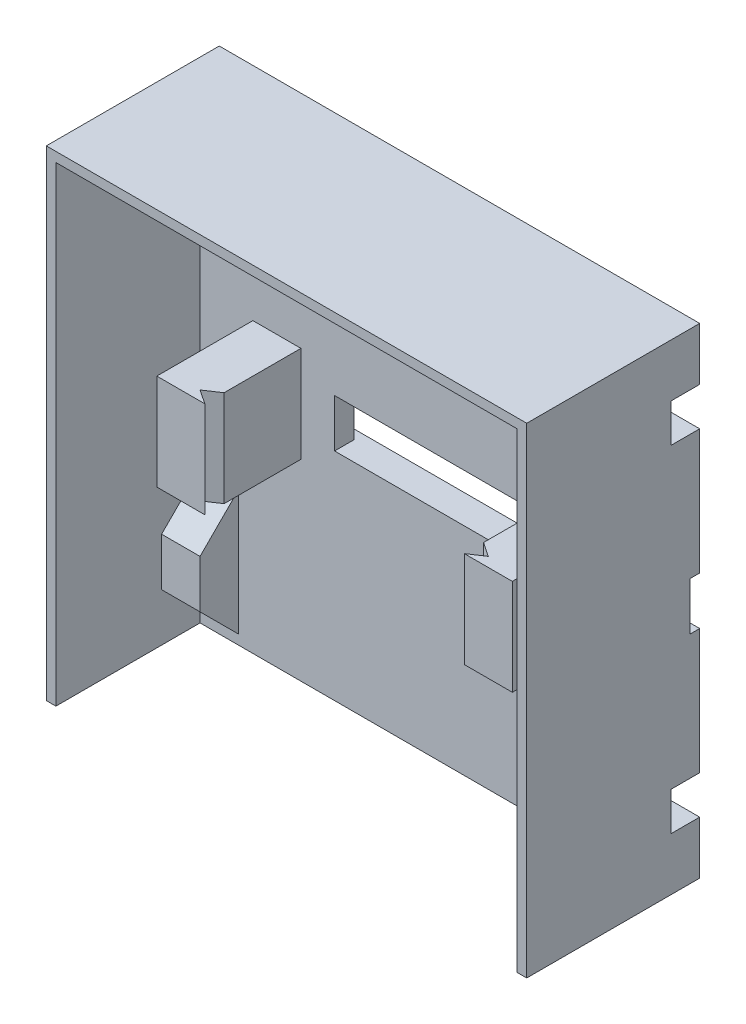
SolidWorks part; units mm, degrees
ref_plane "Přední rovina" through (0, 0, 0) normal (0, 0, 1) x (1, 0, 0)
ref_plane "Horní rovina" through (0, 0, 0) normal (0, 1, 0) x (1, 0, 0)
ref_plane "Pravá rovina" through (0, 0, 0) normal (1, 0, 0) x (0, 0, -1)
sketch "Skica1" plane through (0, 0, 0) normal (0, 0, 1) x (1, 0, 0)
  line L1 (25, 25) -> (-25, 25)
  line L2 (25, 25) -> (25, -25)
  line L3 (25, -25) -> (-25, -25)
  line L4 (-25, 25) -> (-25, -25)
  line L5 (25, 25) -> (-25, -25) construction
  line L6 (25, -25) -> (-25, 25) construction
  point P0 (0, 0)
  point P5 (-27.5, 0)
  point P11 (4.5, 0)
  dimension "D1" = 50
  dimension "D2" = 50
extrude "Přidat vysunutím2" add sketch "Skica1" along normal blind 3 contours L2 L1 L4 L3
sketch "Skica4" plane through (0, 0, 3) normal (0, 0, 1) x (1, 0, 0)
  line L1 (-10, 2.5) -> (10, 2.5)
  line L2 (-10, 2.5) -> (-10, -2.5)
  line L3 (-10, -2.5) -> (10, -2.5)
  line L4 (10, 2.5) -> (10, -2.5)
  line L5 (-10, 2.5) -> (10, -2.5) construction
  line L6 (-10, -2.5) -> (10, 2.5) construction
  line L8 (-25, 25) -> (-25, -25) construction
  point P0 (0, 0)
  dimension "D1" = 5
  dimension "D2" = 20
  dimension "D3" = 15
extrude "Odebrat vysunutím1" cut sketch "Skica4" against normal blind 2
sketch "Skica5" plane through (0, 0, 0) normal (0, 0, -1) x (-1, 0, 0)
  line L10 (25, 25) -> (25, -25) construction
  line L11 (-25, 2.5) -> (25, 2.5)
  line L12 (-25, 2.5) -> (-25, -2.5)
  line L13 (-25, -2.5) -> (25, -2.5)
  line L14 (25, 2.5) -> (25, -2.5)
  line L15 (-25, 2.5) -> (25, -2.5) construction
  line L16 (-25, -2.5) -> (25, 2.5) construction
  point P0 (0, 0)
  dimension "D1" = 5
extrude "Odebrat vysunutím3" cut sketch "Skica5" against normal blind 1 contours L11 L14 L13 L12
sketch "Skica10" plane through (0, 0, 3) normal (0, 0, 1) x (1, 0, 0)
  line L5 (-10, 2.5) -> (-10, -2.5) construction
  line L6 (-13.5, 5) -> (-18.5, 5)
  line L7 (13.5, 5) -> (18.5, 5)
  line L8 (13.5, 5) -> (13.5, -5)
  line L9 (13.5, -5) -> (18.5, -5)
  line L10 (18.5, 5) -> (18.5, -5)
  line L11 (13.5, 5) -> (18.5, -5) construction
  line L12 (13.5, -5) -> (18.5, 5) construction
  line L14 (-13.5, 5) -> (-13.5, -5)
  line L15 (-13.5, -5) -> (-18.5, -5)
  line L16 (-18.5, 5) -> (-18.5, -5)
  line L17 (-13.5, 5) -> (-18.5, -5) construction
  line L18 (-13.5, -5) -> (-18.5, 5) construction
  line L19 (10, -2.5) -> (10, 2.5) construction
  point P0 (-16, 0)
  point P5 (16, 0)
  point P10 (-13.5, 0)
  dimension "D1" = 10
  dimension "D2" = 5
  dimension "D3" = 5
  dimension "D4" = 27
  dimension "D5" = 10
  dimension "D6" = 3.5
  dimension "D7" = 3.5
  dimension "D8" = 0
extrude "Přidat vysunutím6" add sketch "Skica10" along normal blind 10
sketch "Skica12" plane through (0, 5, 0) normal (0, 1, 0) x (1, 0, 0)
  line L0 (-13.5, -13) -> (-13.5, -11)
  line L1 (-13.5, -13) -> (-13.5, -3) construction
  line L2 (-13.5, -11) -> (-15, -12)
  line L3 (-15, -12) -> (-13.5, -13)
  line L4 (13.5, -13) -> (13.5, -11)
  line L5 (13.5, -13) -> (13.5, -3) construction
  line L6 (13.5, -11) -> (15, -12)
  line L7 (15, -12) -> (13.5, -13)
  dimension "D2" = 1.5
  dimension "D1" = 2
  dimension "D3" = 1.5
extrude "Odebrat vysunutím6" cut sketch "Skica12" against normal blind 10
sketch "Skica14" plane through (0, 0, 3) normal (0, 0, 1) x (1, 0, 0)
  line L1 (-25, 25) -> (25, 25)
  line L2 (-25, 25) -> (-25, -25)
  line L3 (-25, -25) -> (25, -25)
  line L4 (25, 25) -> (25, -25)
  line L5 (-24, 24) -> (24, 24)
  line L6 (-24, 24) -> (-24, -25)
  line L7 (-24, -25) -> (24, -25)
  line L8 (24, 24) -> (24, -25)
  line M13 (-25, -25) -> (25, -25)
  line M14 (25, -25) -> (25, 25)
  line M15 (25, 25) -> (-25, 25)
  line M16 (-25, 25) -> (-25, -25)
  dimension "D1" = 1
  dimension "D2" = 1
  dimension "D3" = 1
  dimension "D4" = 0
extrude "Přidat vysunutím9" add sketch "Skica14" along normal blind 15 contours L5 L8 L6 M13 M14 M15 M16 region at (0, 24.2929, 3)
sketch "Skica17" plane through (0, 0, 1) normal (0, 0, -1) x (-1, 0, 0)
  line L0 (-25, 2.5) -> (-25, -2.5) construction
  line L1 (-10, -2.5) -> (-10, 2.5) construction
  line L2 (25, 2.5) -> (25, -2.5) construction
  circle A0 centre (-16, 0) radius 2
  circle A1 centre (16, 0) radius 2
  dimension "D1" = 4
  dimension "D2" = 4
  dimension "D3" = 9
  dimension "D4" = 6
  dimension "D5" = 9
extrude "Odebrat vysunutím8" cut sketch "Skica17" against normal blind 4
sketch "Skica18" plane through (0, 0, 0) normal (0, 0, -1) x (-1, 0, 0)
  line L0 (-25, 25) -> (-25, 2.5) construction
  line L1 (-25, 15) -> (-20, 15)
  line L2 (-25, 15) -> (-25, 20)
  line L3 (-25, 20) -> (-20, 20)
  line L4 (-20, 15) -> (-20, 20)
  line L5 (-25, 25) -> (25, 25) construction
  line L6 (-25, -2.5) -> (-25, -25) construction
  line L7 (-25, -20) -> (-20, -20)
  line L8 (-25, -20) -> (-25, -15)
  line L9 (-25, -15) -> (-20, -15)
  line L10 (-20, -20) -> (-20, -15)
  line L11 (-25, -25) -> (25, -25) construction
  line L12 (0, 25) -> (0, -25)
  line L13 (0, -25) -> (0, 25) construction
  line L14 (25, -15) -> (20, -15)
  line L15 (20, -20) -> (20, -15)
  line L16 (25, -20) -> (20, -20)
  line L17 (25, -20) -> (25, -15)
  line L18 (25, 20) -> (20, 20)
  line L19 (20, 15) -> (20, 20)
  line L20 (25, 15) -> (20, 15)
  line L21 (25, 15) -> (25, 20)
  line M11 (25, 2.5) -> (25, 25)
  line M13 (-25, 25) -> (-25, 2.5)
  dimension "D1" = 10
  dimension "D2" = 5
  dimension "D3" = 5
  dimension "D4" = 10
extrude "Přidat vysunutím10" add sketch "Skica18" against normal blind 7 contours L1 L4 L3 M13 | L20 L18 L19 M11 | L16 L17 L14 L15 | L7 L10 L9 L8 region at (22.5, 17.5, 0) region at (22.5, -17.5, 0) region at (-22.5, -17.5, 0) region at (-22.5, 17.5, 0)
sketch "Skica19" plane through (0, 0, 0) normal (0, 0, -1) x (-1, 0, 0)
  line L0 (-25, 25) -> (-25, 2.5) construction
  line L1 (-25, 19.5) -> (-21, 19.5)
  line L2 (-25, 19.5) -> (-25, 15.5)
  line L3 (-25, 15.5) -> (-21, 15.5)
  line L4 (-21, 19.5) -> (-21, 15.5)
  line L5 (-25, 25) -> (25, 25) construction
  line L6 (-25, -2.5) -> (-25, -25) construction
  line L7 (-25, -15.5) -> (-21, -15.5)
  line L8 (-25, -15.5) -> (-25, -19.5)
  line L9 (-25, -19.5) -> (-21, -19.5)
  line L10 (-21, -15.5) -> (-21, -19.5)
  line L11 (-25, -25) -> (25, -25) construction
  line L12 (0, 25) -> (0, -25)
  line L13 (0, -25) -> (0, 25) construction
  line L14 (25, -19.5) -> (21, -19.5)
  line L15 (21, -15.5) -> (21, -19.5)
  line L16 (25, -15.5) -> (21, -15.5)
  line L17 (25, -15.5) -> (25, -19.5)
  line L18 (25, 15.5) -> (21, 15.5)
  line L19 (21, 19.5) -> (21, 15.5)
  line L20 (25, 19.5) -> (21, 19.5)
  line L21 (25, 19.5) -> (25, 15.5)
  line M10 (-25, -2.5) -> (-25, -25)
  dimension "D1" = 4
  dimension "D2" = 5.5
  dimension "D3" = 4
  dimension "D4" = 5.5
extrude "Odebrat vysunutím10" cut sketch "Skica19" against normal blind 3 contours L10 L7 L9 M10 | L4 L1 L2 L3 | L21 L20 L19 L18 | L15 L14 L17 L16 region at (23, 17.5, 0) region at (23, -17.5, 0) region at (-23, 17.5, 0)
chamfer "Zkosení2" distance 4 angle 45 8 edges at (22, 15, 3) (22, 20, 3) (-22, 20, 3) (-22, 15, 3) (-22, -15, 3) (-22, -20, 3) (22, -20, 3) (22, -15, 3)
sketch "Skica20" plane through (0, 0, 3) normal (0, 0, -1) x (-1, 0, 0)
  line L0 (21, 19.5) -> (21, 15.5) construction
  line L1 (25, 19.5) -> (21, 19.5) construction
  line L2 (-24.6155, 0) -> (25.0232, 0) construction
  line L3 (25.0232, 0) -> (-24.6155, 0)
  line L4 (0, 28.6976) -> (0, -34.0782) construction
  line L5 (-21, -15.5) -> (-21, -19.5) construction
  line L6 (-21, 19.5) -> (-21, 15.5) construction
  line L7 (-25, 19.5) -> (-21, 19.5) construction
  line L8 (-25, -15.5) -> (-21, -15.5) construction
  line L9 (21, -15.5) -> (21, -19.5) construction
  line L10 (25, -15.5) -> (21, -15.5) construction
  circle A0 centre (22.75, 17.5) radius 1.25
  circle A1 centre (22.75, -17.5) radius 1.25
  circle A2 centre (-22.75, -17.5) radius 1.25
  circle A3 centre (-22.75, 17.5) radius 1.25
  point P31 (0, 0)
  dimension "D1" = 2.5
  dimension "D4" = 1.75
  dimension "D6" = 2
  dimension "D2" = 1.75
  dimension "D3" = 2
  dimension "D5" = 1.75
  dimension "D7" = 2
  dimension "D8" = 1.75
  dimension "D9" = 2
extrude "Odebrat vysunutím11" cut sketch "Skica20" against normal blind 3 contours A1 | A2 | A3 | A0
